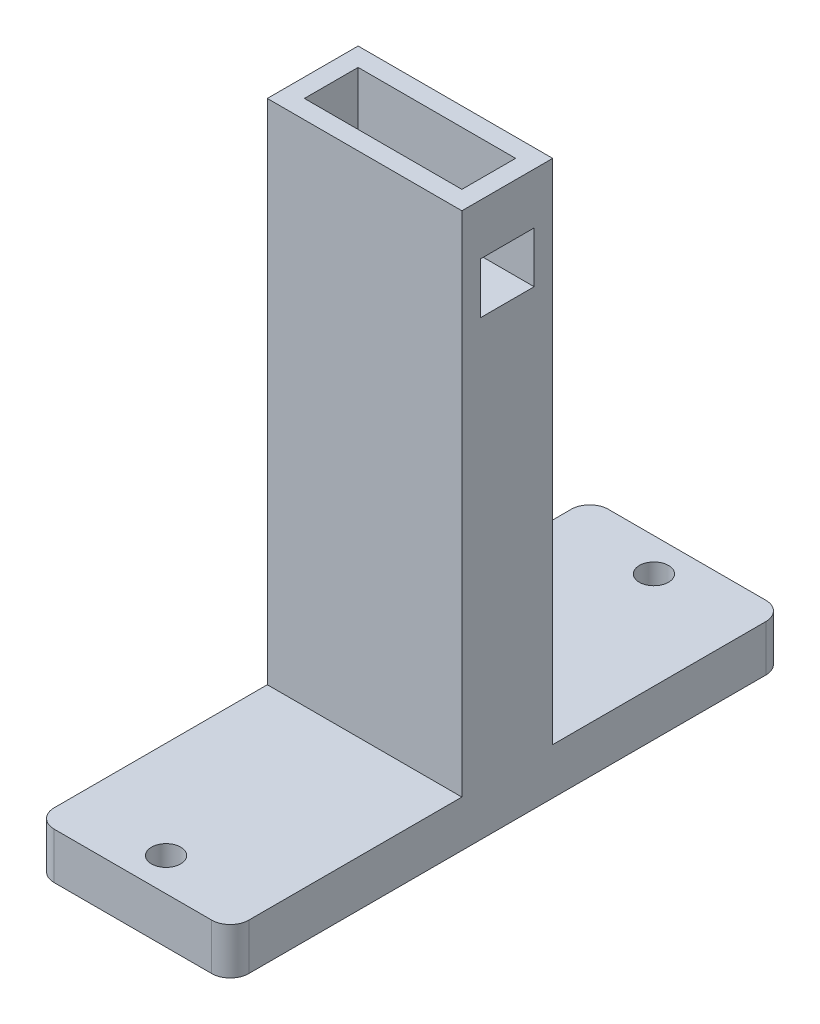
SolidWorks part; units mm, degrees
ref_plane "Front Plane" through (0, 0, 0) normal (0, 0, 1) x (1, 0, 0)
ref_plane "Top Plane" through (0, 0, 0) normal (0, 1, 0) x (1, 0, 0)
ref_plane "Right Plane" through (0, 0, 0) normal (1, 0, 0) x (0, 0, -1)
sketch "Sketch1" plane through (0, 0, 0) normal (0, 1, 0) x (1, 0, 0)
  line L0 (13.335, 6.223) -> (-13.335, 6.223)
  line L1 (10.795, -3.683) -> (-10.795, -3.683) construction
  line L2 (10.795, -3.683) -> (10.795, 3.683) construction
  line L3 (10.795, 3.683) -> (-10.795, 3.683) construction
  line L4 (-10.795, -3.683) -> (-10.795, 3.683) construction
  line L5 (10.795, -3.683) -> (-10.795, 3.683) construction
  line L6 (10.795, 3.683) -> (-10.795, -3.683) construction
  line L7 (-13.335, -6.223) -> (-13.335, 6.223)
  line L8 (13.335, -6.223) -> (-13.335, -6.223)
  line L9 (13.335, -6.223) -> (13.335, 6.223)
  line L10 (-3.2732, 0) -> (4.5518, 0) construction
  line L11 (-13.335, 6.223) -> (13.335, 6.223)
  line L12 (-13.335, 6.223) -> (-13.335, 35.433)
  line L13 (-10.795, 37.973) -> (10.795, 37.973)
  line L14 (13.335, 6.223) -> (13.335, 35.433)
  line L15 (13.335, -6.223) -> (13.335, -35.433)
  line L16 (-10.795, -37.973) -> (10.795, -37.973)
  line L17 (-13.335, -6.223) -> (-13.335, -35.433)
  arc A0 (10.795, 37.973) -> (13.335, 35.433) centre (10.795, 35.433) cw
  arc A1 (-13.335, 35.433) -> (-10.795, 37.973) centre (-10.795, 35.433) cw
  arc A2 (10.795, -37.973) -> (13.335, -35.433) centre (10.795, -35.433) ccw
  arc A3 (-13.335, -35.433) -> (-10.795, -37.973) centre (-10.795, -35.433) ccw
  circle A4 centre (0, 33.433) radius 2
  circle A5 centre (0, -33.433) radius 2
  point P0 (0, 0)
  point P20 (-13.335, 37.973)
  dimension "D5" = 2.54
  dimension "D6" = 4
  dimension "D1" = 21.59
  dimension "D2" = 7.366
  dimension "D4" = 31.75
  dimension "D7" = 4.54
  dimension "D3" = 2.54
extrude "Boss-Extrude1" add sketch "Sketch1" along normal blind 6.35 contours A1 L12 L0 L14 A0 L13 A4 | L17 A3 L16 A2 L15 L8 A5 region at (0, 0, -21.8757) region at (0, 0, 21.8757)
extrude "Boss-Extrude2" add sketch "Sketch1<3>" along normal blind 61.976 contours L8 L9 L0 L7 region at (0, 0, 0)
sketch "Sketch1<3>" plane through (0, 0, 0) normal (0, 1, 0) x (1, 0, 0) same geometry as "Sketch1"
sketch "Sketch2" plane through (0, 61.976, 0) normal (0, 1, 0) x (1, 0, 0)
  line L1 (-13.335, 6.223) -> (13.335, 6.223)
  line L2 (-13.335, 6.223) -> (-13.335, -6.223)
  line L3 (-13.335, -6.223) -> (13.335, -6.223)
  line L4 (13.335, 6.223) -> (13.335, -6.223)
  line L5 (-10.795, 3.683) -> (10.795, 3.683)
  line L6 (-10.795, 3.683) -> (-10.795, -3.683)
  line L7 (-10.795, -3.683) -> (10.795, -3.683)
  line L8 (10.795, 3.683) -> (10.795, -3.683)
extrude "Boss-Extrude3" add sketch "Sketch2" along normal blind 13.97
sketch "Sketch3" plane through (13.335, 0, 0) normal (1, 0, 0) x (0, 0, -1)
  line L0 (-6.223, 0) -> (6.223, 0) construction
  line L1 (-3.683, 68.961) -> (3.683, 68.961)
  line L2 (-3.683, 68.961) -> (-3.683, 61.976)
  line L3 (-3.683, 61.976) -> (3.683, 61.976)
  line L4 (3.683, 68.961) -> (3.683, 61.976)
  line L5 (-6.223, 75.946) -> (-6.223, 6.35) construction
  line L6 (6.223, 75.946) -> (6.223, 6.35) construction
  dimension "D1" = 61.976
  dimension "D2" = 2.54
  dimension "D3" = 2.54
  dimension "D4" = 6.985
extrude "Cut-Extrude1" cut sketch "Sketch3" against normal blind 13.97
